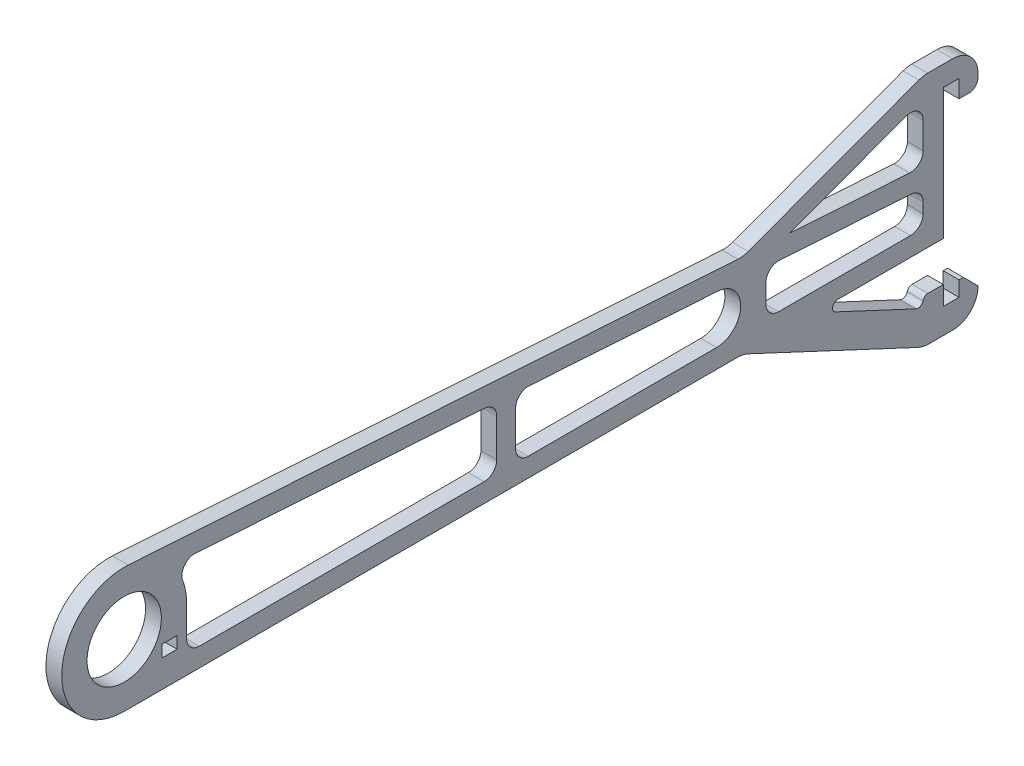
SolidWorks part; units mm, degrees
material "Delrin"
ref_plane "Front Plane" through (0, 0, 0) normal (0, 0, 1) x (1, 0, 0)
ref_plane "Top Plane" through (0, 0, 0) normal (0, 1, 0) x (1, 0, 0)
ref_plane "Right Plane" through (0, 0, 0) normal (1, 0, 0) x (0, 0, -1)
sketch "Sketch1" plane through (0, 0, 0) normal (1, 0, 0) x (0, 0, -1)
  line L0 (0.4103, 6.2604) -> (62.1851, 2.2118)
  line L1 (0, -6.2738) -> (62.1851, -6.2738)
  line L2 (80.264, 8.901) -> (83.2358, 8.901)
  line L3 (4.7788, 4.065) -> (80.264, -0.8821)
  line L4 (4.5027, -4.3688) -> (80.264, -4.3688)
  line L5 (-0.9662, 4.4415) -> (82.6296, -1.0372) construction
  line L6 (0, -4.3688) -> (80.264, -4.3688) construction
  line L7 (80.264, -6.2738) -> (80.264, 8.901) construction
  line L8 (5.3467, -3.556) -> (5.3467, -2.286) construction
  line L9 (5.3467, -2.286) -> (3.7592, -2.286) construction
  line L10 (3.7592, -3.556) -> (3.7592, -2.286) construction
  line L11 (5.3467, -3.556) -> (3.7592, -3.556) construction
  line L12 (5.3467, -3.556) -> (5.3467, -2.286) construction
  line L13 (5.3467, -2.286) -> (3.7592, -2.286) construction
  line L14 (3.7592, -3.556) -> (3.7592, -2.286) construction
  line L15 (5.3467, -3.556) -> (3.7592, -3.556) construction
  line L16 (6.2738, 0) -> (6.2738, -4.3688)
  line L17 (39.3251, 1.8009) -> (39.3251, -4.3688)
  line L18 (37.4201, 1.9258) -> (37.4201, -4.3688)
  line L19 (5.3086, -2.3241) -> (3.7973, -2.3241)
  line L20 (3.7973, -3.5179) -> (3.7973, -2.3241)
  line L21 (5.3086, -3.5179) -> (3.7973, -3.5179)
  line L22 (5.3086, -3.5179) -> (5.3086, -2.3241)
  line L23 (-0.8416, 6.3424) -> (82.7541, 0.8638) construction
  line L24 (84.8868, 5.091) -> (83.8708, 5.091)
  line L25 (83.8708, 5.091) -> (83.8708, 6.869)
  line L26 (83.8708, 6.869) -> (82.296, 6.869)
  line L27 (82.296, 6.869) -> (82.296, -6.2738)
  line L28 (82.296, -12.181) -> (83.8708, -12.181)
  line L29 (83.8708, -12.181) -> (83.8708, -10.657)
  line L30 (83.8708, -10.657) -> (84.3026, -10.657)
  line L31 (85.7758, -12.1302) -> (85.7758, -12.181)
  line L32 (83.2358, -14.721) -> (80.264, -14.721)
  line L33 (80.264, -14.721) -> (80.264, -6.2738) construction
  line L34 (85.7758, 5.98) -> (85.7758, 6.361)
  line L35 (84.3026, -10.657) -> (85.7758, -12.1302)
  line L36 (64.4711, 0.1529) -> (64.4711, -4.3688)
  line L37 (62.1851, 0.3027) -> (62.1851, -4.3688)
  line L38 (62.1851, 2.2118) -> (80.264, 8.901)
  line L39 (66.8488, 1.9062) -> (80.264, 6.8697)
  line L40 (62.1851, -6.2738) -> (80.264, -14.721)
  line L41 (69.3854, -6.2738) -> (80.264, -11.3567)
  line L42 (63.4754, -3.5124) -> (81.5543, -11.9596) construction
  line L43 (62.8461, 0.4252) -> (80.925, 7.1143) construction
  line L44 (69.3854, -6.2738) -> (80.264, -6.2738)
  line L45 (0, -6.2738) -> (80.264, -6.2738) construction
  line L46 (66.8488, 1.9062) -> (80.264, 1.027)
  line L47 (62.1851, -4.3688) -> (62.1851, 49995.6312) construction
  line L48 (80.264, 6.8697) -> (80.264, 1.027)
  line L49 (80.264, -0.8821) -> (80.264, -4.3688)
  line L50 (82.296, -12.181) -> (82.296, -10.276)
  line L51 (80.264, -6.2738) -> (82.296, -6.2738)
  line L52 (82.296, -10.276) -> (80.264, -10.276)
  line L53 (80.264, -10.276) -> (80.264, -11.3567)
  circle A0 centre (0, 0) radius 3.7338
  circle A1 centre (0, 0) radius 6.2738
  arc A2 (83.2358, 8.901) -> (85.7758, 6.361) centre (83.2358, 6.361) cw
  arc A3 (85.7758, -12.181) -> (83.2358, -14.721) centre (83.2358, -12.181) cw
  arc A4 (85.7758, 5.98) -> (84.8868, 5.091) centre (84.8868, 5.98) cw
  point P47 (85.7758, 8.901)
  point P50 (85.7758, -14.721)
  point P53 (85.7758, 5.091)
  point P54 (85.7758, -10.657)
  point P56 (85.7758, -10.657)
  dimension "D1" = 7.4676
  dimension "D2" = 2.54
  dimension "D3" = 5.842
  dimension "D8" = 1.5748
  dimension "D18" = 2.54
  dimension "D19" = 2.54
  dimension "D20" = 0.889
  dimension "D21" = 22.86
  dimension "D5" = 37.4201
  dimension "D10" = 1.905
  dimension "D11" = 1.778
  dimension "D12" = 1.905
  dimension "D4" = 5.3842
  dimension "D9" = 1.5748
  dimension "D14" = 1.524
  dimension "D15" = 3.81
  dimension "D16" = 4.064
  dimension "D17" = 1.905
  dimension "D22" = 19.05
  dimension "D23" = 80.264
  dimension "D24" = 2.032
  dimension "D25" = 2.286
  dimension "D29" = 1.905
  dimension "D6" = 1.905
  dimension "D7" = 1.905
  dimension "D13" = 0.0381
  dimension "D27" = 3.048
  dimension "D28" = 1.905
extrude "Boss-Extrude1" add sketch "Sketch1" along normal blind 1.5875 contours A1 L1 | A1 L4 L16 | L3 L18 L4 L17 | L31 L30 L29 L28 L27 L26 L25 L24 A4 L34 A2 L2 L7 L33 L32 A3 | A1 L21 L20 L19 L22 A0 | L3 L37 L4 L36 region at (0, 3.3483, -31.2395) region at (0, 5.4472, -2.7375) region at (0, -1.2526, -38.3694) region at (0, -3.3092, -5.7604) region at (0, -2.0703, -63.3219)
sketch "Sketch2" plane through (0, 0, -82.296) normal (0, 0, -1) x (-1, 0, 0)
  line L0 (-1.5875, 8.901) -> (0, 8.901) construction
  line L1 (-1.5875, 6.869) -> (0, 6.869) construction
  line L2 (-1.5875, -12.181) -> (0, -12.181) construction
  line L3 (-1.5875, -14.721) -> (0, -14.721) construction
  line L4 (-1.5875, 8.901) -> (0, 8.901)
  line L5 (-1.5875, 6.869) -> (0, 6.869)
  line L6 (-1.5875, -12.181) -> (0, -12.181)
  line L7 (-1.5875, -14.721) -> (0, -14.721)
  line L8 (-1.5875, 8.901) -> (-1.5875, 6.869)
  line L9 (0, 8.901) -> (0, 6.869)
  line L10 (-1.5875, -12.181) -> (-1.5875, -14.721)
  line L11 (0, -12.181) -> (0, -14.721)
fillet "Fillet1" radius 2.54 4 edges at (0.7937, 2.2118, -62.1851) (0.7937, 8.901, -80.264) (0.7937, -6.2738, -62.1851) (0.7937, -14.721, -80.264)
fillet "Fillet2" radius 1.27 12 edges at (0.7937, 4.065, -4.7788) (0.7937, -4.3688, -6.2738) (0.7937, -4.3688, -37.4201) (0.7937, 1.9258, -37.4201) (0.7937, -4.3688, -39.3251) (0.7937, 1.8009, -39.3251) (0.7937, 0.1529, -64.4711) (0.7937, -4.3688, -64.4711) (0.7937, 1.027, -80.264) (0.7937, 6.8697, -80.264) (0.7937, -0.8821, -80.264) (0.7937, -4.3688, -80.264)
fillet "Fillet3" radius 0.508 2 edges at (0.7937, -6.2738, -69.3854) (0.7937, -11.3567, -80.264)
fillet "Fillet4" radius 0.508 1 edges at (0.7937, -10.276, -80.264)
sketch "Sketch4" plane through (1.5875, 0, 0) normal (1, 0, 0) x (0, 0, -1)
  line L0 (40.6782, 1.7122) -> (62.1851, 0.3027) construction
  line L1 (62.1851, 0.3027) -> (62.1851, -4.3688) construction
  line L2 (40.5951, -4.3688) -> (62.1851, -4.3688) construction
  line L3 (59.6686, 0.4676) -> (62.1851, 0.3027)
  line L4 (62.1851, 0.3027) -> (62.1851, -4.3688)
  line L5 (59.5103, -4.3688) -> (62.1851, -4.3688)
  line L6 (61.9311, -1.948) -> (62.1851, -1.948) construction
  line L7 (82.296, 6.869) -> (82.296, -6.2738) construction
  line L8 (40.5951, -4.3688) -> (62.1851, -4.3688) construction
  arc A0 (59.6686, 0.4676) -> (59.5103, -4.3688) centre (59.5103, -1.948) cw
  dimension "D1" = 0.254
extrude "Boss-Extrude2" add sketch "Sketch4" against normal up to surface (1.5875 mm away) up to face at (0, -2.921, -4.5529)
